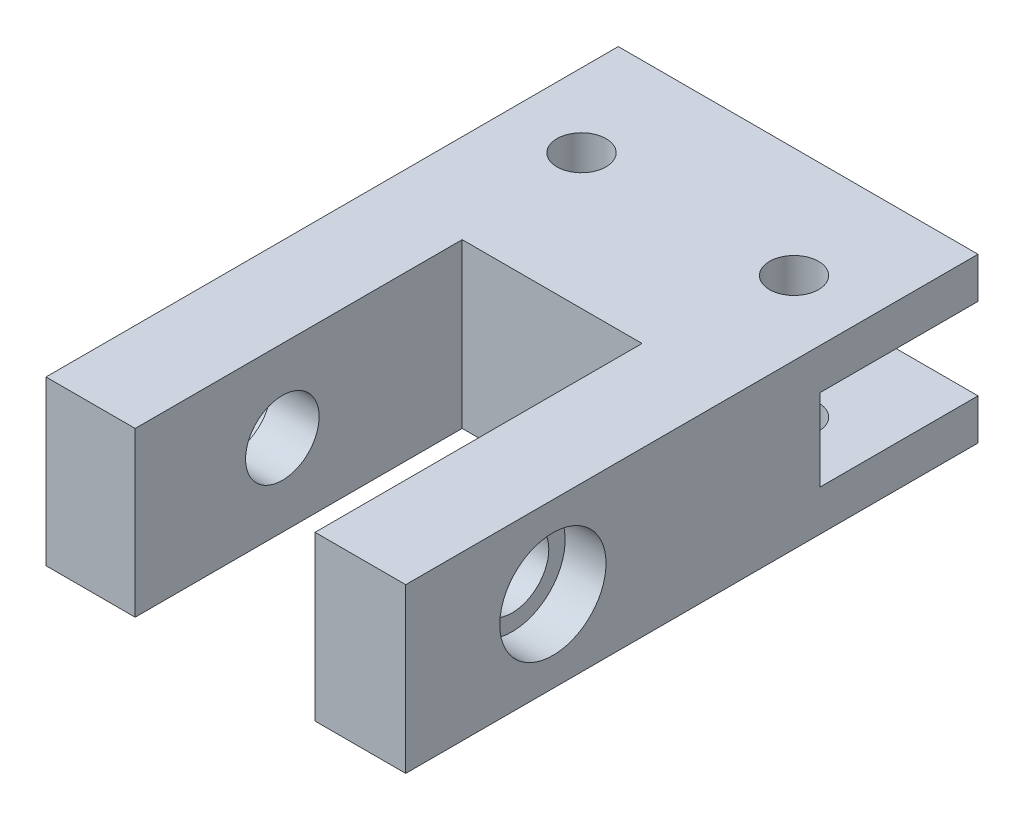
SolidWorks part; units mm, degrees
ref_plane "정면" through (0, 0, 0) normal (0, 0, 1) x (1, 0, 0)
ref_plane "윗면" through (0, 0, 0) normal (0, 1, 0) x (1, 0, 0)
ref_plane "우측면" through (0, 0, 0) normal (1, 0, 0) x (0, 0, -1)
sketch "스케치1" plane through (0, 0, 0) normal (0, 0, 1) x (1, 0, 0)
  line L1 (-22, -10) -> (22, -10)
  line L2 (-22, -10) -> (-22, 10)
  line L3 (-22, 10) -> (22, 10)
  line L4 (22, -10) -> (22, 10)
  line L5 (-22, -10) -> (22, 10) construction
  line L6 (-22, 10) -> (22, -10) construction
  point P0 (0, 0)
  dimension "D1" = 44
  dimension "D2" = 20
extrude "보스-돌출1" add sketch "스케치1" along normal blind 70
sketch "스케치2" plane through (0, 0, 70) normal (0, 0, 1) x (1, 0, 0)
  line L0 (-22, -10) -> (22, -10) construction
  line L1 (-11.0921, -10) -> (10.9079, -10)
  line L2 (-11.0921, -10) -> (-11.0921, 10)
  line L3 (-11.0921, 10) -> (10.9079, 10)
  line L4 (10.9079, -10) -> (10.9079, 10)
  line L5 (22, 10) -> (-22, 10) construction
  dimension "D1" = 22
extrude "컷-돌출1" cut sketch "스케치2" against normal blind 40
sketch "스케치3" plane through (22, 0, 0) normal (1, 0, 0) x (0, 0, -1)
  line L0 (-70, -10) -> (-70, 10) construction
  line L1 (-70, 0) -> (-16.1635, 0) construction
  line L2 (-30, -10) -> (-30, 10) construction
  line L3 (-30, -10) -> (-30, 10) construction
  circle A0 centre (-52, 0) radius 4.5
  dimension "D1" = 9
  dimension "D2" = 22
extrude "컷-돌출2" cut sketch "스케치3" against normal blind 50
sketch "스케치4" plane through (22, 0, 0) normal (-1, 0, 0) x (0, 0, 1)
  circle A0 centre (52, 0) radius 6.5
  dimension "D1" = 13
extrude "컷-돌출4" cut sketch "스케치4" along normal blind 5 contours A0
sketch "스케치5" plane through (0, 10, 0) normal (0, 1, 0) x (1, 0, 0)
  line L2 (22, -70) -> (22, 0) construction
  line L3 (22, 0) -> (-22, 0) construction
  circle A0 centre (13, -13.5) radius 3
  dimension "D1" = 6
  dimension "D2" = 13.5
  dimension "D3" = 9
extrude "컷-돌출5" cut sketch "스케치5" against normal blind 29
mirror "대칭 복사2" about plane through (0, 0, 0) normal (1, 0, 0) of "컷-돌출5", "컷-돌출4"
ref_point "점1"
ref_point "점2"
ref_axis "기준축1" through (33.6861, 10, 13.5) along (-1, 0, 0)
sketch "스케치6" plane through (0, 0, 0) normal (0, 1, 0) x (1, 0, 0)
  line L0 (22, -70) -> (22, 0) construction
  line L2 (2.5, -24) -> (2.5, 0)
  line L3 (22, -19.3492) -> (22, 0)
  line L4 (22, 0) -> (2.5, 0)
  line L7 (17.3492, -24) -> (2.5, -24)
  line L9 (33.6861, -13.5) -> (-20.6842, -13.5) construction
  line L10 (17.3492, -24) -> (22, -19.3492)
  line L11 (13, -13.5) -> (2.5, -24) construction
  line L12 (-22, -19.3492) -> (-22, 0)
  line L14 (0, -24.5) -> (0, 0) construction
  line L15 (-2.5, -24) -> (-2.5, 0)
  line L16 (-17.3492, -24) -> (-2.5, -24)
  line L17 (-17.3492, -24) -> (-22, -19.3492)
  line L18 (-2.5, 0) -> (-22, 0)
  dimension "D1" = 10.5
  dimension "D2" = 10.5
  dimension "D3" = 45
  dimension "D4" = 10.5
extrude "컷-돌출6" cut sketch "스케치6" against normal blind 5 and the other way blind 5
